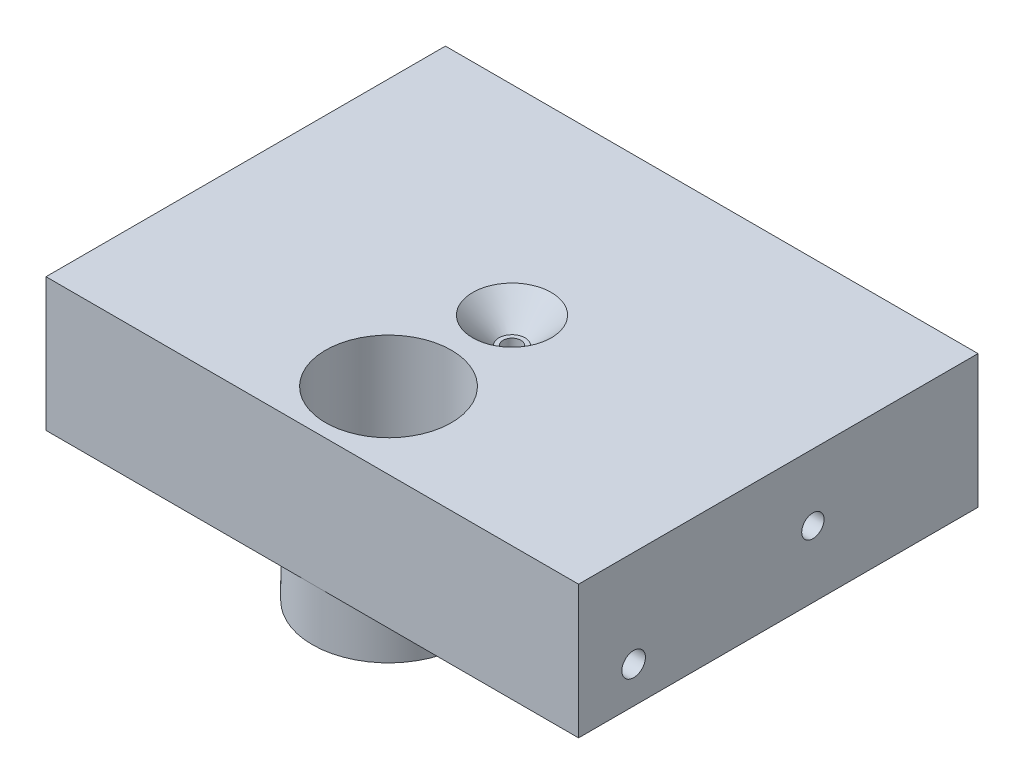
SolidWorks part; units mm, degrees
ref_plane "Front Plane" through (0, 0, 0) normal (0, 0, 1) x (1, 0, 0)
ref_plane "Top Plane" through (0, 0, 0) normal (0, 1, 0) x (1, 0, 0)
ref_plane "Right Plane" through (0, 0, 0) normal (1, 0, 0) x (0, 0, -1)
sketch "Sketch1" plane through (0, 0, 0) normal (0, 1, 0) x (1, 0, 0)
  line L1 (-50.8, 38.1) -> (50.8, 38.1)
  line L2 (-50.8, 38.1) -> (-50.8, -38.1)
  line L3 (-50.8, -38.1) -> (50.8, -38.1)
  line L4 (50.8, 38.1) -> (50.8, -38.1)
  line L5 (-50.8, 38.1) -> (50.8, -38.1) construction
  line L6 (-50.8, -38.1) -> (50.8, 38.1) construction
  point P0 (0, 0)
  dimension "D1" = 101.6
  dimension "D2" = 76.2
extrude "Boss-Extrude1" add sketch "Sketch1" along normal blind 25.4
ref_plane "Plane1" through (0, 25.4, 0) normal (0, 1, 0) x (1, 0, 0)
hole_wizard "CBORE for M3 Hex Head Machine Screw1" positions "Sketch6" profile "Sketch8" counterbore size "M3" standard "ANSI Metric" end condition up to next
sketch "Sketch6" plane through (0, 0, 0) normal (0, -1, 0) x (-1, 0, 0)
  point P0 (0, 0)
sketch "Sketch8" plane through (0, 0, 0) normal (1, 0, 0) x (0, 0, -1)
  line L0 (0, 0) -> (0, 25.4)
  line L1 (0, 25.4) -> (1.7, 25.4)
  line L3 (1.7, 25.4) -> (1.7, 2.3)
  line L4 (1.7, 2.3) -> (4.2, 2.3)
  line L5 (4.2, 2.3) -> (4.2, 0)
  line L7 (4.2, 0) -> (0, 0)
  line L11 (0, -6.35) -> (0, 107.95) construction
  dimension "Thru Hole Dia." = 3.4
  dimension "Thru Hole Depth" = 25.4
  dimension "C'Bore Dia." = 8.4
  dimension "C'Bore Depth" = 2.3
sketch "Sketch9" plane through (0, 25.4, 0) normal (0, 1, 0) x (1, 0, 0)
  circle A0 centre (0, 0) radius 7.5
  dimension "D1" = 15
extrude "Cut-Extrude1" cut sketch "Sketch9" against normal blind 5 draft 45
sketch "Sketch12" plane through (0, 25.4, 0) normal (0, 1, 0) x (1, 0, 0)
  line L0 (0, 0) -> (0, -20) construction
  circle A0 centre (0, -20) radius 5
  circle A1 centre (0, 0) radius 1.7 construction
  dimension "D2" = 10
  dimension "D1" = 20
extrude "Cut-Extrude3" cut sketch "Sketch12" against normal blind 10
sketch "Sketch13" plane through (-50.8, 0, 0) normal (-1, 0, 0) x (0, 0, 1)
  line L0 (-38.1, 12.7) -> (-6.604, 12.7) construction
  line L1 (-38.1, 25.4) -> (-38.1, 0) construction
  circle A0 centre (-6.604, 12.7) radius 2.1336
  dimension "D1" = 4.2672
  dimension "D2" = 31.496
extrude "Cut-Extrude4" cut sketch "Sketch13" against normal through all
sketch "Sketch14" plane through (0, 0, 0) normal (0, -1, 0) x (-1, 0, 0)
  line L0 (0, -38.1) -> (0, -23.56) construction
  line L1 (50.8, -38.1) -> (-50.8, -38.1) construction
  circle A0 centre (0, -23.56) radius 12
  dimension "D1" = 24
  dimension "D2" = 14.54
extrude "Cut-Extrude5" cut sketch "Sketch14" against normal up to next
extrude "Extrude-Thin1" add sketch "Sketch14<2>" along normal blind 10 thin thin type one direction wall 2.54
sketch "Sketch14<2>" plane through (0, 0, 0) normal (0, -1, 0) x (-1, 0, 0) same geometry as "Sketch14"
sketch "Sketch15" plane through (-50.8, 0, 0) normal (-1, 0, 0) x (0, 0, 1)
  line L0 (-6.604, 12.7) -> (27.596, 12.7) construction
  line L1 (27.596, 18.45) -> (27.596, 6.95) construction
  line L2 (-6.604, 12.7) -> (-20.404, 12.7) construction
  line L3 (-20.404, 18.45) -> (-20.404, 6.95) construction
  circle A1 centre (27.596, 6.95) radius 2.25
  point P6 (27.596, 12.7)
  point P12 (-20.404, 12.7)
  dimension "D1" = 34.2
  dimension "D2" = 13.8
  dimension "D5" = 11.5
  dimension "D6" = 11.5
extrude "Cut-Extrude6" cut sketch "Sketch15" against normal blind 10
mirror "Mirror1" about plane through (0, 0, 0) normal (1, 0, 0) of "Cut-Extrude6"
